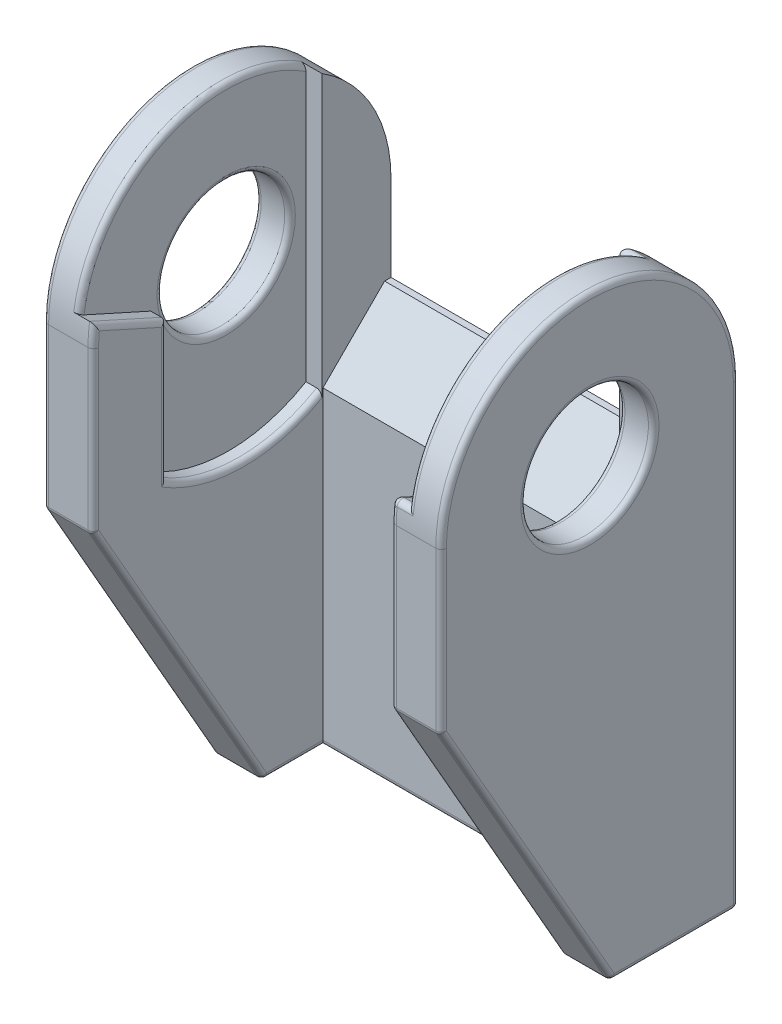
SolidWorks part; units mm, degrees
ref_plane "Plano frontal" through (0, 0, 0) normal (0, 0, 1) x (1, 0, 0)
ref_plane "Plano superior" through (0, 0, 0) normal (0, 1, 0) x (1, 0, 0)
ref_plane "Plano direito" through (0, 0, 0) normal (1, 0, 0) x (0, 0, -1)
sketch "Esboço1" plane through (0, 0, 0) normal (0, 0, 1) x (1, 0, 0)
  line L1 (-9.355, -14.26) -> (9.355, -14.26)
  line L2 (-9.355, -14.26) -> (-9.355, 14.26)
  line L3 (-9.355, 14.26) -> (9.355, 14.26)
  line L4 (9.355, -14.26) -> (9.355, 14.26)
  line L5 (-9.355, -14.26) -> (9.355, 14.26) construction
  line L6 (-9.355, 14.26) -> (9.355, -14.26) construction
  point P0 (0, 0)
  dimension "D1" = 28.52
  dimension "D2" = 18.71
extrude "Ressalto-extrusão1" add sketch "Esboço1" along normal blind 14
sketch "Esboço2" plane through (0, 0, 14) normal (0, 0, 1) x (1, 0, 0)
  line L0 (-9.355, 14.26) -> (-9.355, -14.26) construction
  line L1 (-7, -17.4948) -> (7, -17.4948)
  line L2 (-7, -17.4948) -> (-7, 17.4948)
  line L3 (-7, 17.4948) -> (7, 17.4948)
  line L4 (7, -17.4948) -> (7, 17.4948)
  line L5 (-7, -17.4948) -> (7, 17.4948) construction
  line L6 (-7, 17.4948) -> (7, -17.4948) construction
  line L7 (9.355, -14.26) -> (9.355, 14.26) construction
  line L8 (9.355, 14.26) -> (-9.355, 14.26) construction
  point P0 (0, 0)
  dimension "D1" = 14
extrude "Corte-extrusão3" cut sketch "Esboço2" against normal blind 10.8
sketch "Esboço3" plane through (-9.355, 0, 0) normal (-1, 0, 0) x (0, 0, 1)
  line L3 (0, 7.26) -> (-0.5166, 7.26)
  line L4 (-8.4483, 7.26) -> (-4.1145, 15.5066)
  line L5 (-4.1145, 15.5066) -> (7.2516, 15.8746)
  line L7 (-0.5166, 7.26) -> (-8.4483, 7.26)
  line L8 (7.2516, 15.8746) -> (19.1901, 14.8524)
  line L9 (19.1901, 14.8524) -> (17.2685, 7.26)
  line L10 (17.2685, 7.26) -> (14, 7.26)
  arc A1 (14, 7.26) -> (0, 7.26) centre (7, 7.26) ccw
extrude "Corte-extrusão4" cut sketch "Esboço3" against normal blind 29.8
sketch "Esboço4" plane through (-9.355, 0, 0) normal (-1, 0, 0) x (0, 0, 1)
  circle A1 centre (7, 7.26) radius 3
  dimension "D1" = 6
extrude "Corte-extrusão5" cut sketch "Esboço4" against normal blind 29.8
sketch "Esboço5" plane through (0, 0, 0) normal (0, 0, -1) x (-1, 0, 0)
  line L0 (-7, 14.511) -> (-7, 3.24)
  line L2 (-7, 3.24) -> (7, 3.24)
  line L3 (7, 14.511) -> (6.6705, 14.511)
  line L4 (7, 14.511) -> (7, 3.24)
  line L5 (-7, 14.511) -> (6.6705, 14.511)
extrude "Corte-extrusão6" cut sketch "Esboço5" against normal blind 29.8
chamfer "Chanfro1" distance 2.9 angle 45 1 edges at (0, 3.24, 3.2)
sketch "Esboço6" plane through (0, 0, 3.2) normal (0, 0, 1) x (1, 0, 0)
  line L3 (7, -14.26) -> (-7, -14.26) construction
  line L7 (-0.0381, -11.7595) -> (0, -14.26)
  circle A0 centre (0, -2.26) radius 1.5
  circle A1 centre (0, -10.26) radius 1.5
  dimension "D3" = 3
  dimension "D4" = 3
extrude "Corte-extrusão7" cut sketch "Esboço6" along normal blind 19.8 and the other way blind 36 contours A0 | A1 region at (0, -2.26, 3.2) region at (0, -10.26, 3.2)
chamfer "Chanfro2" distance 0.8 angle 45 2 edges at (-1.5, -10.26, 3.2) (-1.5, -2.26, 3.2)
sketch "Esboço14" plane through (0, 3.24, 0) normal (0, 1, 0) x (1, 0, 0)
  line L1 (-7.75, -3.25) -> (-7.75, -10.55)
  line L2 (-7.75, -3.25) -> (7.75, -3.25)
  line L4 (-7.75, -10.55) -> (7.75, -10.55)
  line L6 (7.75, -10.55) -> (7.75, -3.25)
  point P4 (0, 0)
  dimension "D2" = 7.3
extrude "Corte-extrusão9" cut sketch "Esboço14" against normal blind 3 and the other way blind 17
sketch "Esboço18" plane through (-7, 0, 0) normal (1, 0, 0) x (0, 0, -1)
  line L0 (-10.55, 6.7665) -> (-13.9243, 8.2868)
  line L1 (-10.55, 13.293) -> (-10.55, 0.24) construction
  line L2 (-10.55, 6.7665) -> (-10.55, 16.2473)
  line L3 (-10.55, 16.2473) -> (-15.3277, 16.2473)
  line L4 (-15.3277, 16.2473) -> (-16.9332, 9.3191)
  line L5 (-16.9332, 9.3191) -> (-13.9243, 8.2868)
  arc A0 (-10.55, 13.293) -> (-14, 7.26) centre (-7, 7.26) ccw construction
extrude "Corte-extrusão10" cut sketch "Esboço18" against normal blind 0.75
sketch "Esboço19" plane through (7, 0, 0) normal (-1, 0, 0) x (0, 0, 1)
  line L0 (10.55, 6.7665) -> (13.9162, 8.3397)
  line L1 (10.55, 0.24) -> (10.55, 13.293) construction
  line L2 (13.9162, 8.3397) -> (15.4539, 12.8792)
  line L3 (15.4539, 12.8792) -> (9.6634, 16.8938)
  line L4 (9.6634, 16.8938) -> (10.55, 13.293)
  line L5 (10.55, 13.293) -> (10.55, 6.7665)
  arc A0 (14, 7.26) -> (10.55, 13.293) centre (7, 7.26) ccw construction
extrude "Corte-extrusão11" cut sketch "Esboço19" against normal blind 0.75
sketch "Esboço21" plane through (9.355, 0, 0) normal (1, 0, 0) x (0, 0, -1)
  line L1 (-14, -14.26) -> (0, -14.26) construction
  line L2 (-13.9162, -0.3903) -> (-14.3745, 0.4126)
  line L3 (-13.9162, -0.3903) -> (-6, -14.26)
  line L5 (-22.7425, -0.3903) -> (-21.8805, -13.649)
  line L6 (-21.8805, -13.649) -> (-8.0468, -16.6456)
  line L7 (-8.0468, -16.6456) -> (-6, -14.26)
  line L8 (-14.3745, 0.4126) -> (-22.7425, -0.3903)
extrude "Corte-extrusão12" cut sketch "Esboço21" against normal blind 33.75 and the other way blind 13
sketch "Esboço22" plane through (-7, 0, 0) normal (1, 0, 0) x (0, 0, -1)
  line L0 (-3.25, 0.24) -> (-10.55, 0.24) construction
  line L2 (-3.25, 0.24) -> (-10.55, 0.24)
  arc A0 (-3.25, 0.24) -> (-10.55, 0.24) centre (-6.9, 6.4013) cw
extrude "Corte-extrusão14" cut sketch "Esboço22" against normal blind 0.75
sketch "Esboço23" plane through (7, 0, 0) normal (-1, 0, 0) x (0, 0, 1)
  line L2 (3.25, 0.24) -> (10.55, 0.24)
  arc A0 (3.25, 0.24) -> (10.55, 0.24) centre (6.9, 6.4013) ccw
extrude "Corte-extrusão15" cut sketch "Esboço23" against normal blind 0.75
fillet "Filete1" radius 0.25 40 edges at (7, 5.25, 0) (9.355, -3.5, 0) (9.355, 3.5083, 14) (7, 3.5083, 14) (-9.355, -3.5, 0) (-9.355, 14.26, 7) (-7, 7.7748, 13.981) (-7, -14.26, 4.6) (0, -14.26, 3.2) (7, -14.26, 4.6) (9.355, -14.26, 3) (0, -14.26, 0) (-9.355, -14.26, 3) (8.1775, -0.2435, 14) (9.355, -7.2517, 10) (8.1775, -14.26, 6) (7, -7.2517, 10) (7.375, 13.1708, 3.25) (7, 10.6327, 0.8661) (9.355, 14.26, 7) (7, 7.8015, 13.979) (7.375, 8.3397, 13.9162) (7.75, 13.6364, 9.8881) (-9.355, 3.5083, 14) (-7, 3.5083, 14) (-8.1775, -14.26, 6) (-9.355, -7.2517, 10) (-8.1775, -0.2435, 14) (-7, -7.2517, 10) (-7, -0.76, 6.9) (-7, 7.5267, 12.2371) (-7, 3.5033, 10.55) (9.355, 7.26, 10) (-7.75, 7.26, 4) (7.75, 7.26, 10) (-9.355, 7.26, 10) (7, -0.76, 6.9) (7, 3.5033, 10.55) (7, 7.5531, 12.2331) (-7.75, 13.6254, 9.9124)
